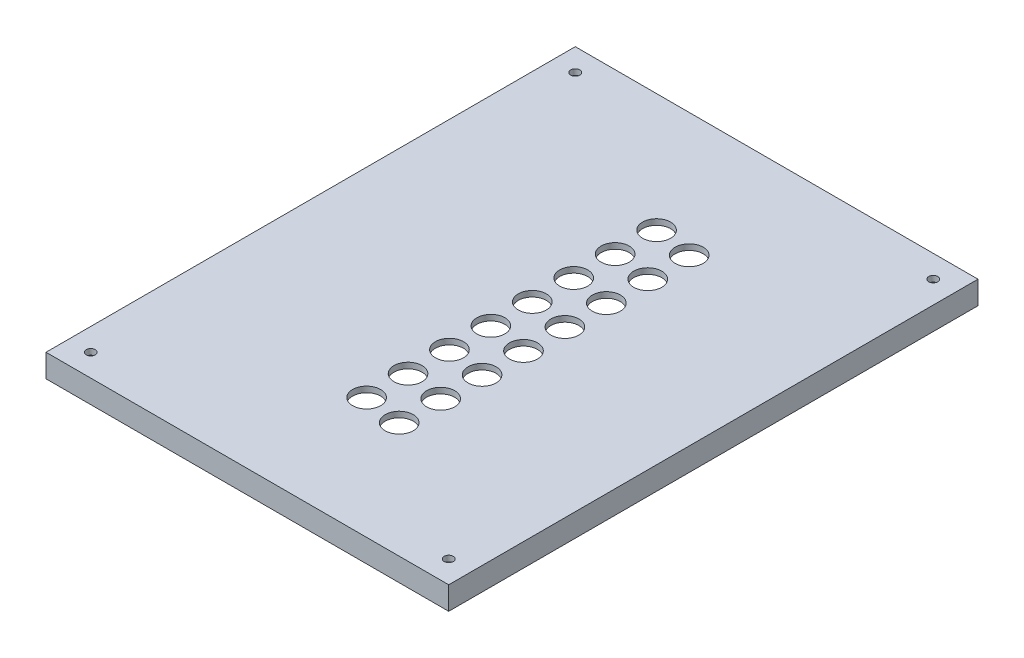
SolidWorks part; units mm, degrees
ref_plane "Front Plane" through (0, 0, 0) normal (0, 0, 1) x (1, 0, 0)
ref_plane "Top Plane" through (0, 0, 0) normal (0, 1, 0) x (1, 0, 0)
ref_plane "Right Plane" through (0, 0, 0) normal (1, 0, 0) x (0, 0, -1)
sketch "Sketch1" plane through (0, 0, 0) normal (0, 1, 0) x (1, 0, 0)
  line L0 (-173.4212, 169.0006) -> (-173.4212, -110.3994)
  line L1 (-173.4212, -110.3994) -> (36.1288, -110.3994)
  line L2 (36.1288, -110.3994) -> (36.1288, 169.0006)
  line L3 (36.1288, 169.0006) -> (-173.4212, 169.0006)
  circle A0 centre (-167.4212, -104.3994) radius 2.5273
  circle A1 centre (-167.4212, 163.0006) radius 2.5273
  circle A2 centre (30.1288, -104.3994) radius 2.5273
  circle A3 centre (30.1288, 163.0006) radius 2.5273
  dimension "D1" = 5.0546
  dimension "D2" = 30.1288
  dimension "D3" = 36.1288
  dimension "D4" = 167.4212
  dimension "D5" = 173.4212
  dimension "D6" = 163.0006
  dimension "D7" = 169.0006
  dimension "D8" = 104.3994
  dimension "D9" = 110.3994
extrude "Boss-Extrude1" add sketch "Sketch1" along normal blind 3.175
sketch "Sketch2" plane through (0, 3.175, 0) normal (0, 1, 0) x (1, 0, 0)
  line L20 (-179.7712, -116.7494) -> (42.4788, -116.7494)
  line L21 (42.4788, -116.7494) -> (42.4788, 175.3506)
  line L22 (-179.7712, 175.3506) -> (-179.7712, -116.7494)
  line L23 (42.4788, 175.3506) -> (-179.7712, 175.3506)
  line L24 (-179.7712, -116.7494) -> (42.4788, -116.7494)
  line L25 (42.4788, -116.7494) -> (42.4788, 175.3506)
  line L26 (-179.7712, 175.3506) -> (-179.7712, -116.7494)
  line L27 (42.4788, 175.3506) -> (-179.7712, 175.3506)
  line L38 (-175.0087, -111.9869) -> (37.7163, -111.9869)
  line L39 (37.7163, -111.9869) -> (37.7163, 170.5881)
  line L40 (-175.0087, 170.5881) -> (-175.0087, -111.9869)
  line L41 (37.7163, 170.5881) -> (-175.0087, 170.5881)
  line L42 (-175.0087, -111.9869) -> (37.7163, -111.9869)
  line L43 (37.7163, -111.9869) -> (37.7163, 170.5881)
  line L44 (-175.0087, 170.5881) -> (-175.0087, -111.9869)
  line L45 (37.7163, 170.5881) -> (-175.0087, 170.5881)
  line M15 (36.1288, 169.0006) -> (-173.4212, 169.0006)
  line M16 (-173.4212, 169.0006) -> (-173.4212, -110.3994)
  line M17 (-173.4212, -110.3994) -> (36.1288, -110.3994)
  line M18 (36.1288, -110.3994) -> (36.1288, 169.0006)
  dimension "D1" = 6.35
  dimension "D2" = 1.5875
extrude "Boss-Extrude2" add sketch "Sketch2" against normal blind 12.7 separate body
ref_plane "Plane1" through (-175.0087, 3.175, -170.5881) normal (-1, 0, 0) x (0, 0, 1)
extrude "Boss-Extrude3" add sketch "Sketch2<2>" against normal up to surface (3.175 mm away) contours L43 L45 L44 L42 M15 M18 M17 M16 region at (-174.655, 3.175, -29.3006) up to face at (-68.6462, 0, -29.3006)
sketch "Sketch2<2>" plane through (0, 3.175, 0) normal (0, 1, 0) x (1, 0, 0) same geometry as "Sketch2"
hole_wizard "39/64 (0.60938) Diameter Hole1" positions "Sketch4" profile "Sketch5" hole size "39/64" standard "ANSI Inch" end condition through all
sketch "Sketch4" plane through (0, 3.175, 0) normal (0, 1, 0) x (1, 0, 0)
  point P0 (-69.6462, 110.0867)
  point P3 (-48.6462, 107.0867)
  point P6 (-69.6462, 87.2267)
  point P9 (-48.6462, 84.2267)
  point P12 (-48.6462, 61.3667)
  point P15 (-69.6462, 64.3667)
  point P18 (-69.6462, 41.5067)
  point P21 (-48.6462, 38.5067)
  point P24 (-48.6462, 15.6467)
  point P27 (-69.6462, 18.6467)
  point P30 (-69.6462, -4.2133)
  point P33 (-48.6462, -7.2133)
  point P36 (-48.6462, -30.0733)
  point P39 (-69.6462, -27.0733)
  point P42 (-69.6462, -49.9333)
  point P45 (-48.6462, -52.9333)
sketch "Sketch5" plane through (-69.6462, 3.175, -110.0867) normal (1, 0, 0) x (0, 0, 1)
  line L0 (0, 0) -> (0, 12.7)
  line L1 (0, 12.7) -> (7.7391, 12.7)
  line L2 (7.7391, 12.7) -> (7.7391, 0)
  line L5 (7.7391, 0) -> (0, 0)
  line L11 (0, -6.35) -> (0, 107.95) construction
  dimension "Thru Hole Dia." = 15.4783
  dimension "Thru Hole Depth" = 12.7
